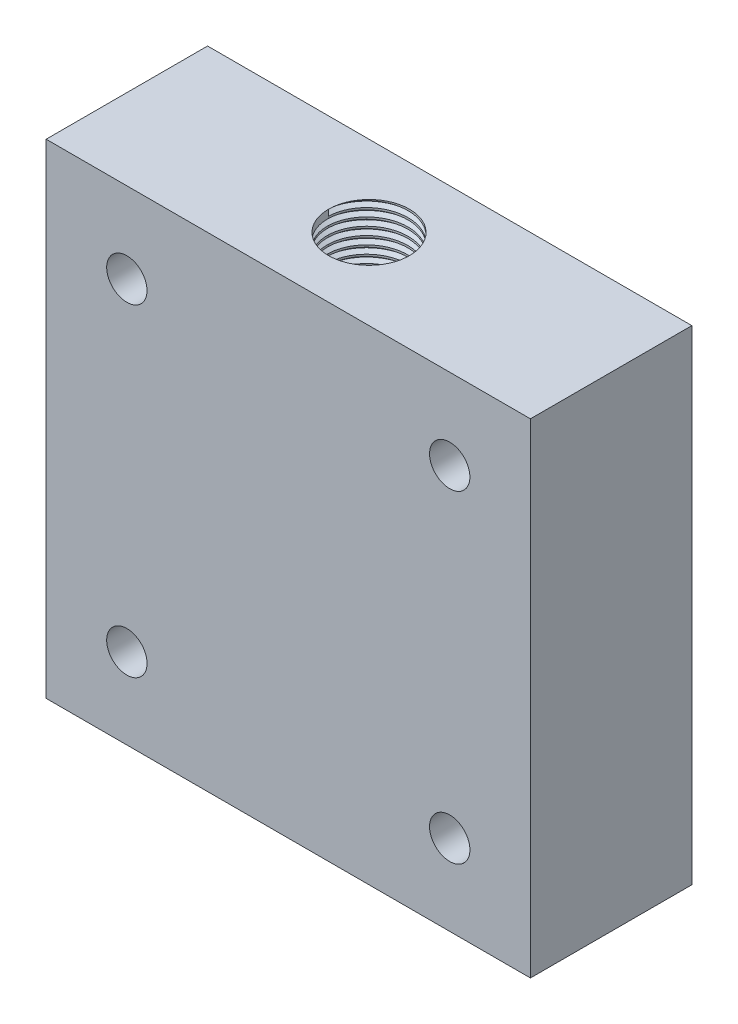
SolidWorks part; units mm, degrees
ref_plane "Front Plane" through (0, 0, 0) normal (0, 0, 1) x (1, 0, 0)
ref_plane "Top Plane" through (0, 0, 0) normal (0, 1, 0) x (1, 0, 0)
ref_plane "Right Plane" through (0, 0, 0) normal (1, 0, 0) x (0, 0, -1)
sketch "Sketch2" plane through (0, 0, 0) normal (0, 0, 1) x (1, 0, 0)
  line L1 (-38.1, -38.1) -> (38.1, -38.1)
  line L2 (-38.1, -38.1) -> (-38.1, 38.1)
  line L3 (-38.1, 38.1) -> (38.1, 38.1)
  line L4 (38.1, -38.1) -> (38.1, 38.1)
  line L5 (-38.1, -38.1) -> (38.1, 38.1) construction
  line L6 (-38.1, 38.1) -> (38.1, -38.1) construction
  point P0 (0, 0)
  dimension "D1" = 76.2
  dimension "D2" = 76.2
extrude "Boss-Extrude1" add sketch "Sketch2" along normal blind 25.4
sketch "Sketch3" plane through (0, 0, 0) normal (0, 0, -1) x (-1, 0, 0)
  circle A0 centre (0, 0) radius 25.4
  circle A1 centre (0, 0) radius 19.05
  dimension "D1" = 50.8
  dimension "D2" = 38.1
extrude "Cut-Extrude1" cut sketch "Sketch3" against normal blind 3.81
sketch "Sketch5" plane through (0, 38.1, 0) normal (0, 1, 0) x (1, 0, 0)
  line L0 (38.1, 0) -> (-38.1, 0) construction
  circle A0 centre (0, -12.7) radius 6.35
  point P4 (0, 0)
  dimension "D1" = 12.7
  dimension "D2" = 12.7
extrude "Cut-Extrude12" cut sketch "Sketch5" against normal blind 38.1
thread "Thread1" pitch 1.27 method cut profile "Thread Profile2" start angle 0, offset 0, length 12.7, pitch 1.27, diameter 12.7
ref_plane "Plane2" through (-6.35, 38.1, 12.7) normal (0, 0, 1) x (-1, 0, 0)
sketch "Thread Profile2" plane through (-6.35, 38.1, 12.7) normal (0, 0, 1) x (-1, 0, 0)
  line L0 (0, 0) -> (0, 1.27) construction
  line L1 (0, 0) -> (0.6874, 0.3969)
  line L2 (0.6874, 0.3969) -> (0.6874, 0.5556)
  line L3 (0.6874, 0.5556) -> (0, 0.9525)
  line L4 (0.6874, 0.4762) -> (0, 0.4762) construction
  line L11 (0, 0) -> (0, 0.9525)
  point P2 (0, 0)
  dimension "Pitch" = 1.27
  dimension "Profile_Angle" = 60
  dimension "Profile_Land" = 0.1588
  dimension "Profile_Height" = 0.6874
sketch "Sketch25" plane through (0, 0, 0) normal (0, 0, -1) x (-1, 0, 0)
  circle A0 centre (0, 0) radius 12.7
  dimension "D1" = 25.4
extrude "Cut-Extrude15" cut sketch "Sketch25" against normal blind 12.7
sketch "Sketch26" plane through (0, 0, 25.4) normal (0, 0, 1) x (1, 0, 0)
  line L0 (38.1, 38.1) -> (-38.1, 38.1) construction
  line L3 (-38.1, 38.1) -> (-38.1, -38.1) construction
  circle A0 centre (-25.4, 25.4) radius 3.175
  circle A1 centre (25.4, 25.4) radius 3.175
  circle A2 centre (25.4, -25.4) radius 3.175
  circle A3 centre (-25.4, -25.4) radius 3.175
  point P15 (0, 0)
  dimension "D1" = 6.35
  dimension "D2" = 12.7
  dimension "D3" = 12.7
  dimension "D4" = 4
extrude "Cut-Extrude16" cut sketch "Sketch26" against normal through all
chamfer "Chamfer1" distance 2.54 angle 45 1 edges at (-12.7, 0, 0)
chamfer "Chamfer2" distance 0.508 angle 45 2 edges at (-25.4, 0, 0) (-19.05, 0, 0)
fillet "Fillet1" radius 0.762 1 edges at (-25.4, 0, 3.81)
